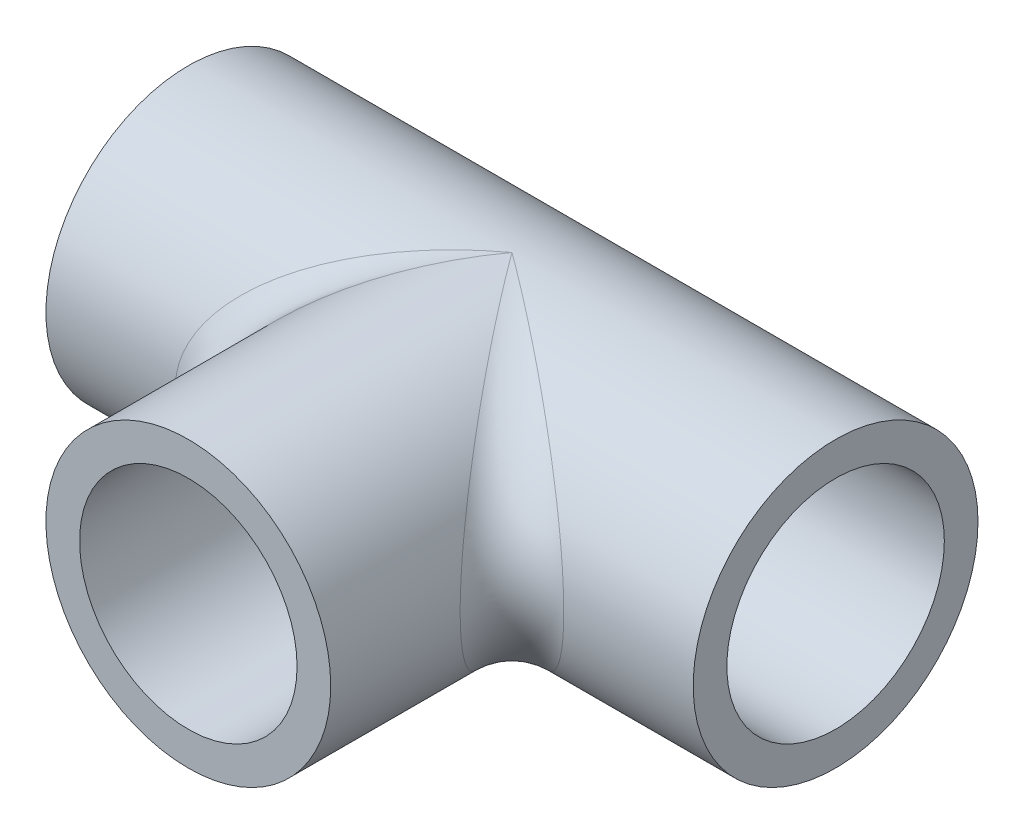
SolidWorks part; units mm, degrees
ref_plane "Front Plane" through (0, 0, 0) normal (0, 0, 1) x (1, 0, 0)
ref_plane "Top Plane" through (0, 0, 0) normal (0, 1, 0) x (1, 0, 0)
ref_plane "Right Plane" through (0, 0, 0) normal (1, 0, 0) x (0, 0, -1)
sketch "Sketch1" plane through (0, 0, 0) normal (1, 0, 0) x (0, 0, -1)
  circle A0 centre (0, 0) radius 13.97
  circle A1 centre (0, 0) radius 10.668
  dimension "D1" = 27.94
  dimension "D2" = 21.336
extrude "Boss-Extrude1" add sketch "Sketch1" along normal blind 63.5
sketch "Sketch2" plane through (0, 0, 0) normal (0, 0, 1) x (1, 0, 0)
  line L0 (0, 13.97) -> (0, -13.97) construction
  circle A0 centre (31.75, 0) radius 13.97
  dimension "D1" = 31.75
  dimension "D2" = 27.94
extrude "Boss-Extrude2" add sketch "Sketch2" along normal blind 31.75
sketch "Sketch3" plane through (0, 0, 31.75) normal (0, 0, 1) x (1, 0, 0)
  circle A0 centre (31.75, 0) radius 10.668
  dimension "D1" = 21.336
extrude "Cut-Extrude1" cut sketch "Sketch3" against normal blind 31.75
sketch "Sketch4" plane through (0, 0, 0) normal (-1, 0, 0) x (0, 0, 1)
  circle A0 centre (0, 0) radius 10.668
extrude "Cut-Extrude2" cut sketch "Sketch4" against normal blind 64.77
fillet "Fillet1" radius 5.08 2 edges at (45.72, 0, 13.97) (17.78, 0, 13.97)
